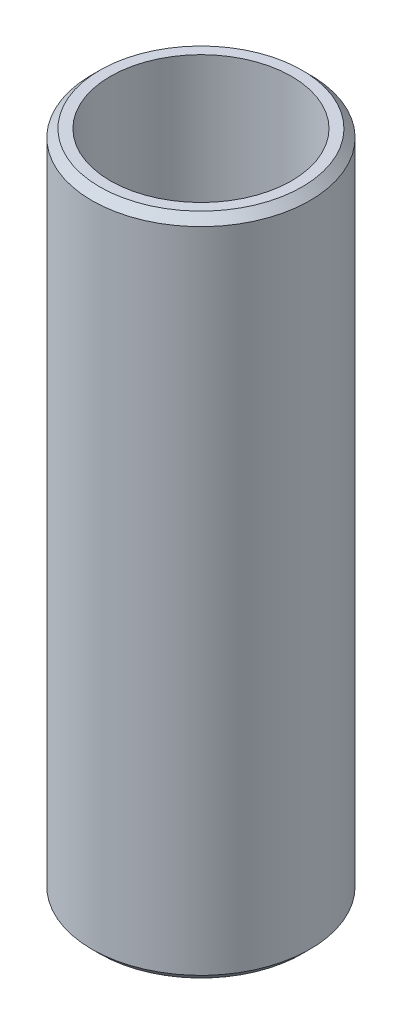
SolidWorks part; units mm, degrees
ref_plane "Front Plane" through (0, 0, 0) normal (0, 0, 1) x (1, 0, 0)
ref_plane "Top Plane" through (0, 0, 0) normal (0, 1, 0) x (1, 0, 0)
ref_plane "Right Plane" through (0, 0, 0) normal (1, 0, 0) x (0, 0, -1)
sketch "Sketch1" plane through (0, 0, 0) normal (0, 1, 0) x (1, 0, 0)
  circle A0 centre (0, 0) radius 32.5
  dimension "SHAFT_OD" = 65
extrude "Boss-Extrude1" add sketch "Sketch1" along normal blind 197.9984
sketch "Sketch2" plane through (0, 0, 0) normal (0, 1, 0) x (1, 0, 0)
  circle A0 centre (0, 0) radius 26.9993
  dimension "BORE_D" = 53.9987
extrude "Cut-Extrude1" cut sketch "Sketch2" along normal through all
chamfer "Chamfer1" distance 2.3491 angle 45 2 edges at (0, 197.9984, 32.5) (0, 0, 32.5)
